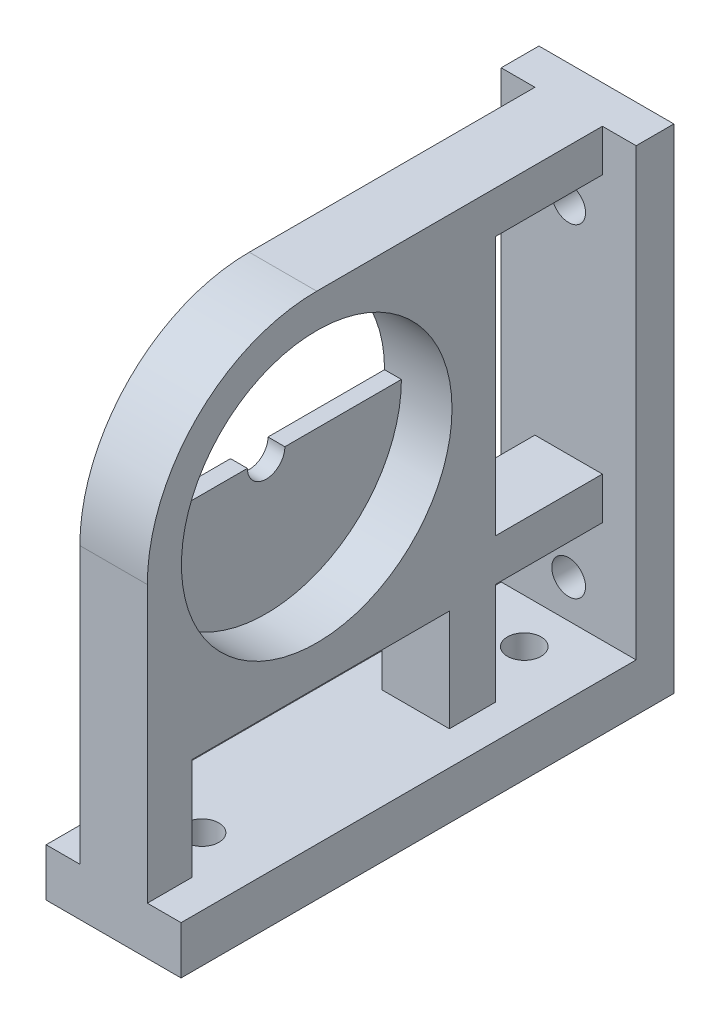
SolidWorks part; units mm, degrees
ref_plane "Front Plane" through (0, 0, 0) normal (0, 0, 1) x (1, 0, 0)
ref_plane "Top Plane" through (0, 0, 0) normal (0, 1, 0) x (1, 0, 0)
ref_plane "Right Plane" through (0, 0, 0) normal (1, 0, 0) x (0, 0, -1)
sketch "Sketch1" plane through (0, 0, 0) normal (1, 0, 0) x (0, 0, -1)
  line L11 (0, 31.8822) -> (31.8822, 31.8822)
  line L12 (31.8822, 31.8822) -> (60.8746, 31.8822)
  line L16 (60.8746, 31.8822) -> (60.8746, -60.96)
  line L17 (-31.8822, 0) -> (-31.8822, -60.96)
  line L18 (60.8746, -60.96) -> (-31.8822, -60.96)
  circle A1 centre (0, 0) radius 25.4635
  arc A3 (0, 31.8822) -> (-31.8822, 0) centre (0, 0) ccw
extrude "Boss-Extrude1" add sketch "Sketch1" along normal blind 12.7
sketch "Sketch8" plane through (12.7, 0, 0) normal (1, 0, 0) x (0, 0, -1)
  line L0 (-31.8822, -60.96) -> (60.8746, -60.96) construction
  line L1 (60.8746, 31.8822) -> (53.7706, 31.8822)
  line L2 (60.8746, 31.8822) -> (60.8746, -60.96)
  line L3 (60.8746, -60.96) -> (53.7706, -60.96)
  line L4 (53.7706, 31.8822) -> (53.7706, -51.9379)
  line L5 (-31.8822, 0) -> (-31.8822, -60.96) construction
  line L6 (53.7706, -60.96) -> (-31.8822, -60.96)
  line L8 (53.7706, -51.9379) -> (-31.8822, -51.9379)
  line L9 (-31.8822, -60.96) -> (-31.8822, -51.9379)
extrude "Boss-Extrude2" add sketch "Sketch8" along normal blind 6.35 and the other way blind 19.05
sketch "Sketch2" plane through (0, 0, 0) normal (0, 1, 0) x (1, 0, 0)
  circle A0 centre (6.35, 0) radius 3.175
extrude "Cut-Extrude1" [suppressed] cut sketch "Sketch2" along normal through all
sketch "Sketch10" plane through (0, 0, 31.8822) normal (0, 0, 1) x (1, 0, 0)
  line L0 (12.7, 0) -> (0, 0) construction
  circle A0 centre (6.35, 0) radius 3.175
extrude "Cut-Extrude6" [suppressed] cut sketch "Sketch10" against normal blind 8.128
fillet "Fillet1" [suppressed] radius 2.54
mirror "Mirror1" [suppressed] about plane through (0, 0, 0) normal (0, 0, 1)
fillet "Fillet2" [suppressed] radius 5.08
sketch "Sketch4" plane through (0, 0, 0) normal (-1, 0, 0) x (0, 0, 1)
  line L4 (-53.7706, 23.9633) -> (-33.6922, 23.9633)
  line L5 (-33.6922, 23.9633) -> (-33.6922, -24.8177)
  line L6 (-24.9665, -32.7419) -> (23.4543, -32.7419)
  line L7 (23.4543, -32.7419) -> (23.4543, -51.9379)
  line L8 (23.4543, -51.9379) -> (-24.9665, -51.9379)
  line L9 (-53.7706, -51.9379) -> (-53.7706, -32.7419)
  line L10 (-33.6922, -32.7419) -> (-33.6922, -51.9379)
  line L11 (-24.9665, -51.9379) -> (-24.9665, -32.7419)
  line L12 (-33.6922, -51.9379) -> (-53.7706, -51.9379)
  line L13 (-33.6922, -32.7419) -> (-53.7706, -32.7419)
  line L14 (-33.6922, -24.8177) -> (-53.7706, -24.8177)
  line L15 (-53.7706, -24.8177) -> (-53.7706, 23.9633)
extrude "Cut-Extrude2" cut sketch "Sketch4" against normal blind 26.162
sketch "Sketch5" plane through (0, 0, -60.8746) normal (0, 0, -1) x (-1, 0, 0)
  circle A0 centre (-6.35, 16.187) radius 3.175
  circle A1 centre (-6.35, -44.7886) radius 3.175
extrude "Cut-Extrude3" cut sketch "Sketch5" against normal blind 11.43
sketch "Sketch6" plane through (0, -60.96, 0) normal (0, -1, 0) x (1, 0, 0)
  circle A0 centre (6.35, 15.24) radius 3.175
  circle A1 centre (6.35, -45.4106) radius 3.175
extrude "Cut-Extrude4" cut sketch "Sketch6" against normal blind 11.43
sketch "Sketch9" plane through (0, 0, 0) normal (-1, 0, 0) x (0, 0, 1)
  line L1 (-33.6922, -24.8177) -> (-71.3105, -24.8177)
  line L2 (-33.6922, -24.8177) -> (-33.6922, 42.9585)
  line L3 (-33.6922, 42.9585) -> (-71.3105, 42.9585)
  line L4 (-71.3105, -24.8177) -> (-71.3105, 42.9585)
extrude "Cut-Extrude5" [suppressed] cut sketch "Sketch9" against normal blind 41.656 and the other way blind 46.736
fillet "Fillet3" [suppressed] radius 33.02
sketch "Sketch11" plane through (0, 0, 0) normal (-1, 0, 0) x (0, 0, 1)
  circle A0 centre (0, 0) radius 25.4
extrude "Cut-Extrude7" [suppressed] cut sketch "Sketch11" against normal blind 20.828
sketch "Sketch12" plane through (0, 0, 0) normal (-1, 0, 0) x (0, 0, 1)
  line L0 (25.4635, 0) -> (3.5273, 0)
  line L1 (-3.5273, 0) -> (-25.4635, 0)
  circle A0 centre (0, 0) radius 25.4635 construction
  arc A1 (-25.4635, 0) -> (25.4635, 0) centre (0, 0) ccw
  arc A2 (-3.5273, 0) -> (3.5273, 0) centre (0, 0) ccw
extrude "Boss-Extrude3" add sketch "Sketch12" against normal blind 3.175
